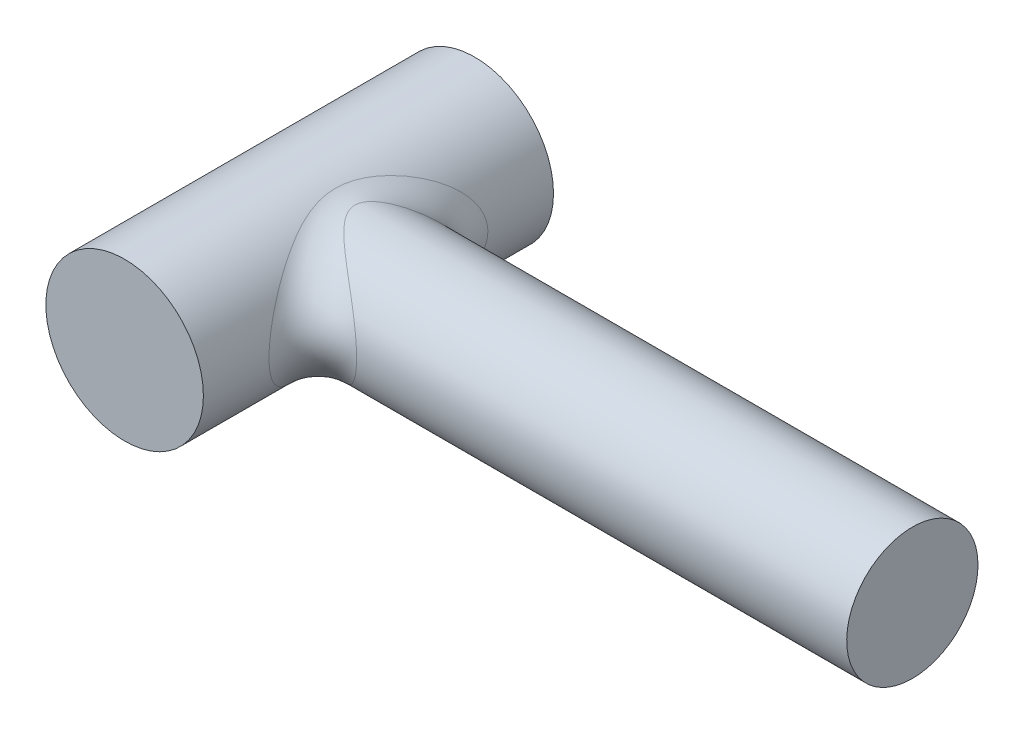
SolidWorks part; units mm, degrees
material "moto_orange"
ref_plane "Front Plane" through (0, 0, 0) normal (0, 0, 1) x (1, 0, 0)
ref_plane "Top Plane" through (0, 0, 0) normal (0, 1, 0) x (1, 0, 0)
ref_plane "Right Plane" through (0, 0, 0) normal (1, 0, 0) x (0, 0, -1)
sketch "Sketch1" plane through (0, 0, 0) normal (0, 0, 1) x (1, 0, 0)
  circle A0 centre (0, 0) radius 9
  dimension "D1" = 18
extrude "Boss-Extrude1" add sketch "Sketch1" along normal mid plane 40
sketch "Sketch2" plane through (0, 0, 0) normal (1, 0, 0) x (0, 0, -1)
  circle A0 centre (0, 0) radius 7.5
  dimension "D1" = 15
extrude "Boss-Extrude2" add sketch "Sketch2" along normal blind 70
fillet "Fillet3" radius 5 1 edges at (8.9947, 0.3088, -7.4936)
